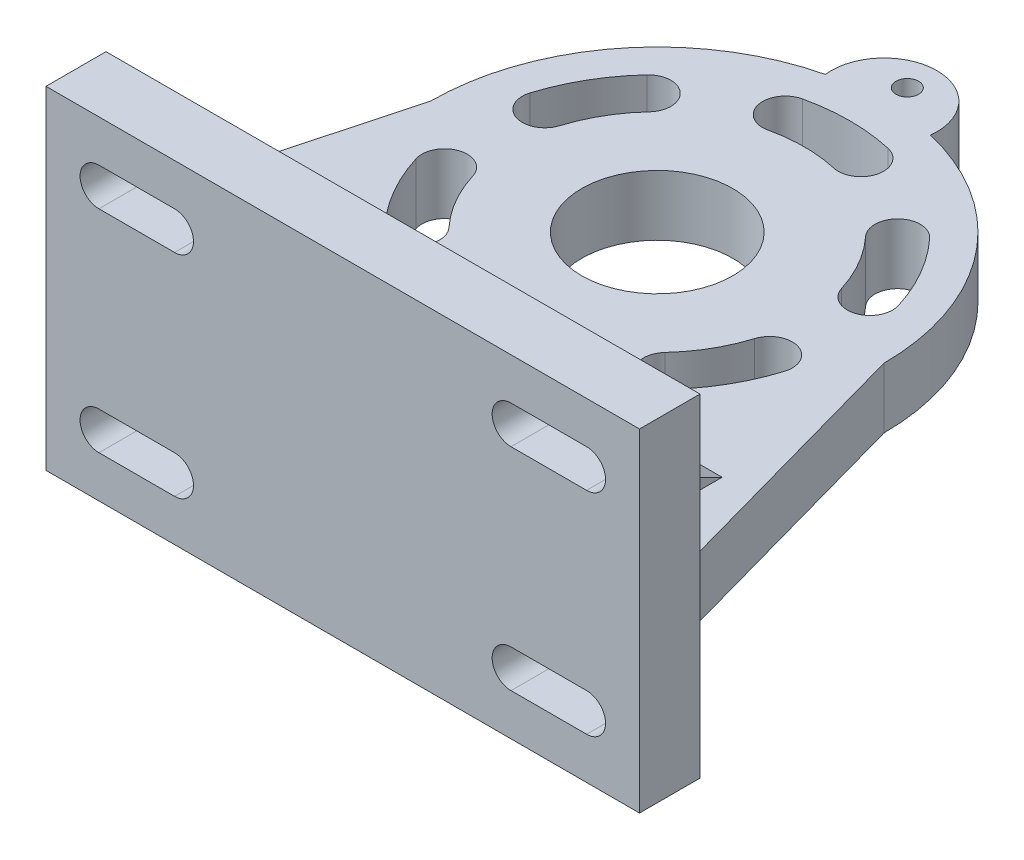
SolidWorks part; units mm, degrees
material "ABS"
ref_plane "Front Plane" through (0, 0, 0) normal (0, 0, 1) x (1, 0, 0)
ref_plane "Top Plane" through (0, 0, 0) normal (0, 1, 0) x (1, 0, 0)
ref_plane "Right Plane" through (0, 0, 0) normal (1, 0, 0) x (0, 0, -1)
sketch "Sketch1" plane through (0, 0, 0) normal (0, 1, 0) x (1, 0, 0)
  circle A0 centre (0, 0) radius 30
  dimension "D1" = 60
extrude "Boss-Extrude1" add sketch "Sketch1" along normal blind 8 contours A0
sketch "Sketch10" plane through (0, 8, 0) normal (0, 1, 0) x (1, 0, 0)
  arc A0 (5, 21.9374) -> (-5, 21.9374) centre (0, 0) ccw construction
  arc A1 (5.6667, 24.8624) -> (-5.6667, 24.8624) centre (0, 0) ccw
  arc A2 (4.3333, 19.0124) -> (-4.3333, 19.0124) centre (0, 0) ccw
  arc A3 (4.3333, 19.0124) -> (5.6667, 24.8624) centre (5, 21.9374) ccw
  arc A4 (-5.6667, 24.8624) -> (-4.3333, 19.0124) centre (-5, 21.9374) ccw
  arc A5 (21.4984, 6.6386) -> (16.4984, 15.2988) centre (0, 0) ccw construction
  arc A6 (24.3648, 7.5237) -> (18.6981, 17.3387) centre (0, 0) ccw
  arc A7 (18.6319, 5.7534) -> (14.2986, 13.259) centre (0, 0) ccw
  arc A8 (18.6319, 5.7534) -> (24.3648, 7.5237) centre (21.4984, 6.6386) ccw
  arc A9 (18.6981, 17.3387) -> (14.2986, 13.259) centre (16.4984, 15.2988) ccw
  arc A10 (16.4984, -15.2988) -> (21.4984, -6.6386) centre (0, 0) ccw construction
  arc A11 (18.6981, -17.3387) -> (24.3648, -7.5237) centre (0, 0) ccw
  arc A12 (14.2986, -13.259) -> (18.6319, -5.7534) centre (0, 0) ccw
  arc A13 (14.2986, -13.259) -> (18.6981, -17.3387) centre (16.4984, -15.2988) ccw
  arc A14 (24.3648, -7.5237) -> (18.6319, -5.7534) centre (21.4984, -6.6386) ccw
  arc A15 (-5, -21.9374) -> (5, -21.9374) centre (0, 0) ccw construction
  arc A16 (-5.6667, -24.8624) -> (5.6667, -24.8624) centre (0, 0) ccw
  arc A17 (-4.3333, -19.0124) -> (4.3333, -19.0124) centre (0, 0) ccw
  arc A18 (-4.3333, -19.0124) -> (-5.6667, -24.8624) centre (-5, -21.9374) ccw
  arc A19 (5.6667, -24.8624) -> (4.3333, -19.0124) centre (5, -21.9374) ccw
  arc A20 (-21.4984, -6.6386) -> (-16.4984, -15.2988) centre (0, 0) ccw construction
  arc A21 (-24.3648, -7.5237) -> (-18.6981, -17.3387) centre (0, 0) ccw
  arc A22 (-18.6319, -5.7534) -> (-14.2986, -13.259) centre (0, 0) ccw
  arc A23 (-18.6319, -5.7534) -> (-24.3648, -7.5237) centre (-21.4984, -6.6386) ccw
  arc A24 (-18.6981, -17.3387) -> (-14.2986, -13.259) centre (-16.4984, -15.2988) ccw
  arc A25 (-16.4984, 15.2988) -> (-21.4984, 6.6386) centre (0, 0) ccw construction
  arc A26 (-18.6981, 17.3387) -> (-24.3648, 7.5237) centre (0, 0) ccw
  arc A27 (-14.2986, 13.259) -> (-18.6319, 5.7534) centre (0, 0) ccw
  arc A28 (-14.2986, 13.259) -> (-18.6981, 17.3387) centre (-16.4984, 15.2988) ccw
  arc A29 (-24.3648, 7.5237) -> (-18.6319, 5.7534) centre (-21.4984, 6.6386) ccw
  circle A30 centre (0, 0) radius 10
  point P5 (0, 22.5)
  point P12 (19.4856, 11.25)
  point P19 (19.4856, -11.25)
  point P26 (0, -22.5)
  point P34 (-19.4856, -11.25)
  point P41 (-19.4856, 11.25)
  point P46 (0, 0)
  dimension "D4" = 6
  dimension "D3" = 10
  dimension "D2" = 22.5
  dimension "D1" = 3
  dimension "D5" = 20
extrude "Cut-Extrude3" cut sketch "Sketch10" against normal blind 10
sketch "Sketch11" plane through (0, 8, 0) normal (0, 1, 0) x (1, 0, 0)
  line L0 (-30, 0) -> (-30, -30)
  line L1 (-30, -30) -> (30, -30)
  line L2 (30, 0) -> (30, -30)
  circle A0 centre (0, 0) radius 30 construction
sketch "Sketch12" plane through (0, 8, 0) normal (0, 1, 0) x (1, 0, 0)
  line L3 (-30, 0) -> (-39.1321, -33.7876)
  line L4 (-39.1321, -33.7876) -> (39.374, -33.7213)
  line L5 (30, 0) -> (39.374, -33.7213)
  circle A2 centre (0, 0) radius 30 construction
  circle A3 centre (0, 0) radius 30
  circle M27 centre (0, 0) radius 30
  dimension "D1" = 35
  dimension "D2" = 35
extrude "Boss-Extrude2" add sketch "Sketch12" against normal blind 8 contours M27 | M27 region at (0, 8, 30.8547)
sketch "Sketch13" plane through (0, 8, 0) normal (0, 1, 0) x (1, 0, 0)
  line L6 (-39.1321, -33.7876) -> (39.374, -33.7213)
  line L8 (-39.1321, -41.7213) -> (39.374, -41.7213)
  line L10 (-39.1321, -33.7876) -> (-39.1321, -41.7213)
  line L12 (39.374, -33.7213) -> (39.374, -41.7213)
  dimension "D1" = 8
extrude "Boss-Extrude3" add sketch "Sketch13" along normal blind 18 and the other way blind 26
ref_plane "Plane1" through (-29.1321, 0, 0) normal (-1, 0, 0) x (0, 0, 1)
sketch "Sketch15" plane through (-29.1321, 0, 0) normal (-1, 0, 0) x (0, 0, 1)
  line L5 (23.7876, 8) -> (33.7876, 13)
  line L6 (0, 8) -> (33.7876, 8) construction
  line L7 (33.7876, 8) -> (33.7876, 26) construction
  dimension "D1" = 5
  dimension "D2" = 10
rib "Rib22" sketch "Sketch15" sketch "Sketch15" thickness 6 extrusion direction parallel to sketch draft on no parameters "D1"=6
ref_plane "Plane2" through (0.1209, 0, 0) normal (-1, 0, 0) x (0, 0, 1)
mirror "Mirror1" about plane through (0.1209, 0, 0) normal (-1, 0, 0) of "Rib22"
ref_plane "Plane3" through (0, 4, 0) normal (0, 1, 0) x (1, 0, 0)
mirror "Mirror2" [suppressed] about plane through (0, 4, 0) normal (0, 1, 0)
sketch "Sketch16" plane through (0, 8, 0) normal (0, 1, 0) x (1, 0, 0)
  arc A5 (6.9522, 29.1833) -> (-6.9522, 29.1833) centre (0, 30) ccw
  arc A6 (30, 0) -> (-30, 0) centre (0, 0) ccw construction
  circle A7 centre (0, 33.0745) radius 1.5
  arc A8 (6.9522, 29.1833) -> (-6.9522, 29.1833) centre (0, 0) ccw
  dimension "D1" = 14
  dimension "D2" = 3
extrude "Boss-Extrude4" add sketch "Sketch16" against normal blind 8
sketch "Sketch17" plane through (0.0285, 0, 33.7546) normal (-0.0008, 0, -1) x (-1, 0, 0.0008)
  line L0 (-32.3455, 17.9698) -> (-22.3455, 17.9698) construction
  line L1 (-32.3455, 20.4698) -> (-22.3455, 20.4698)
  line L2 (-32.3455, 15.4698) -> (-22.3455, 15.4698)
  line L3 (-32.3455, 15.4698) -> (-32.3455, 12.9421) construction
  line L5 (-0.0924, 26) -> (-0.0924, 15.4698) construction
  line L8 (-32.3455, 12.9698) -> (-32.3455, 8) construction
  line L11 (-39.3455, 26) -> (39.1607, 26) construction
  line L14 (-39.3455, 4) -> (-32.9188, 4) construction
  line L17 (-26.3455, 12.9723) -> (-32.3455, 12.9698) construction
  line L18 (-39.3455, 0) -> (-39.3455, 8) construction
  line L19 (4.4, 4) -> (-4.4, 4) construction
  line L20 (32.1607, 17.9698) -> (22.1607, 17.9698) construction
  line L21 (32.1607, 20.4698) -> (22.1607, 20.4698)
  line L22 (32.1607, 15.4698) -> (22.1607, 15.4698)
  line L23 (32.1607, -9.9698) -> (22.1607, -9.9698) construction
  line L24 (32.1607, -12.4698) -> (22.1607, -12.4698)
  line L25 (32.1607, -7.4698) -> (22.1607, -7.4698)
  line L26 (-32.3455, -9.9698) -> (-22.3455, -9.9698) construction
  line L27 (-32.3455, -12.4698) -> (-22.3455, -12.4698)
  line L28 (-32.3455, -7.4698) -> (-22.3455, -7.4698)
  arc A0 (-32.3455, 20.4698) -> (-32.3455, 15.4698) centre (-32.3455, 17.9698) ccw
  arc A1 (-22.3455, 15.4698) -> (-22.3455, 20.4698) centre (-22.3455, 17.9698) ccw
  arc A8 (32.1607, 20.4698) -> (32.1607, 15.4698) centre (32.1607, 17.9698) cw
  arc A9 (22.1607, 15.4698) -> (22.1607, 20.4698) centre (22.1607, 17.9698) cw
  arc A10 (32.1607, -12.4698) -> (32.1607, -7.4698) centre (32.1607, -9.9698) ccw
  arc A11 (22.1607, -7.4698) -> (22.1607, -12.4698) centre (22.1607, -9.9698) ccw
  arc A12 (-32.3455, -12.4698) -> (-32.3455, -7.4698) centre (-32.3455, -9.9698) cw
  arc A13 (-22.3455, -7.4698) -> (-22.3455, -12.4698) centre (-22.3455, -9.9698) cw
  point P2 (-27.3455, 17.9698)
  point P25 (27.1607, 17.9698)
  point P32 (27.1607, -9.9698)
  point P39 (-27.3455, -9.9698)
  dimension "D2" = 2.5
  dimension "D1" = 10
  dimension "D3" = 0
  dimension "D4" = 5
extrude "Cut-Extrude4" cut sketch "Sketch17" against normal blind 8
